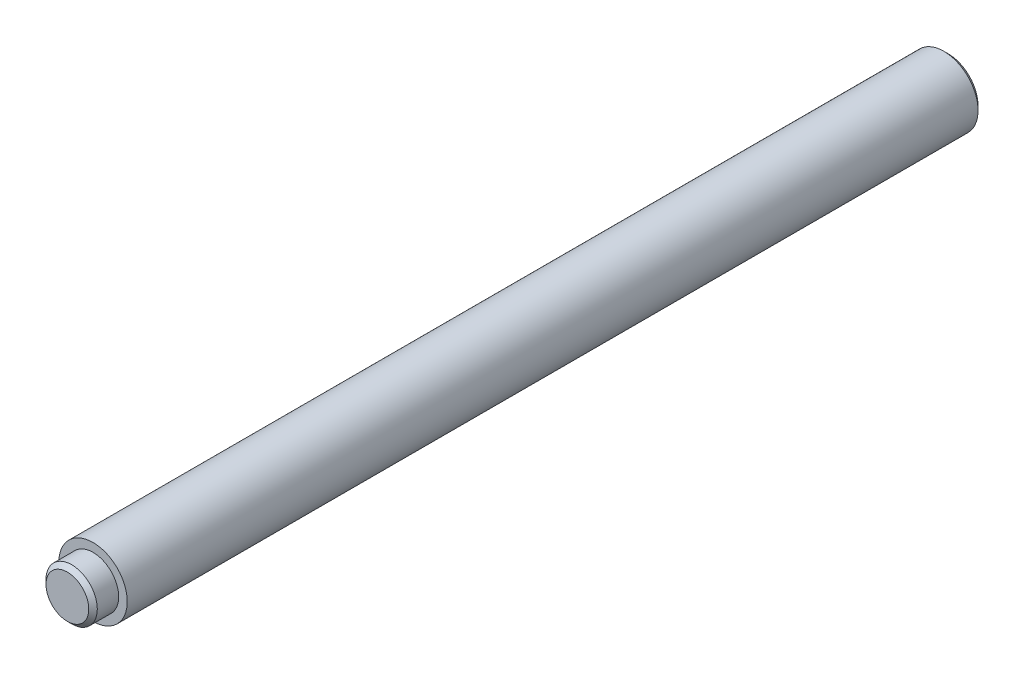
SolidWorks part; units mm, degrees
material "6061-T6 (SS)"
ref_plane "Front" through (0, 0, 0) normal (0, 0, 1) x (1, 0, 0)
ref_plane "Top" through (0, 0, 0) normal (0, 1, 0) x (1, 0, 0)
ref_plane "Right" through (0, 0, 0) normal (1, 0, 0) x (0, 0, -1)
ref_axis "side-side" through (80.9, 0, 0) along (-1, 0, 0)
ref_axis "up-down" through (0, 50, 0) along (0, -1, 0)
ref_axis "front-back" through (0, 0, -80.9) along (0, 0, 1)
sketch "Sketch1" plane through (0, 0, 0) normal (1, 0, 0) x (0, 0, -1)
  line L0 (-3, 0) -> (-55.8451, 0) construction
  line L1 (-3, 0) -> (100, 0)
  line L2 (0, 3) -> (0, 4)
  line L3 (0, 4) -> (100, 4)
  line L4 (100, 0) -> (100, 4)
  line L6 (0, 3) -> (-3, 3)
  line L9 (-3, 3) -> (-3, 0)
  point P0 (0, 0)
  dimension "D1" = 8
  dimension "D2" = 6
  dimension "D3" = 3
  dimension "D4" = 100
revolve "Revolve1" add sketch "Sketch1" angle 360 about L0
chamfer "Chamfer1" distance 0.5 angle 45 2 edges at (-4, 0, -100) (-3, 0, 3)
